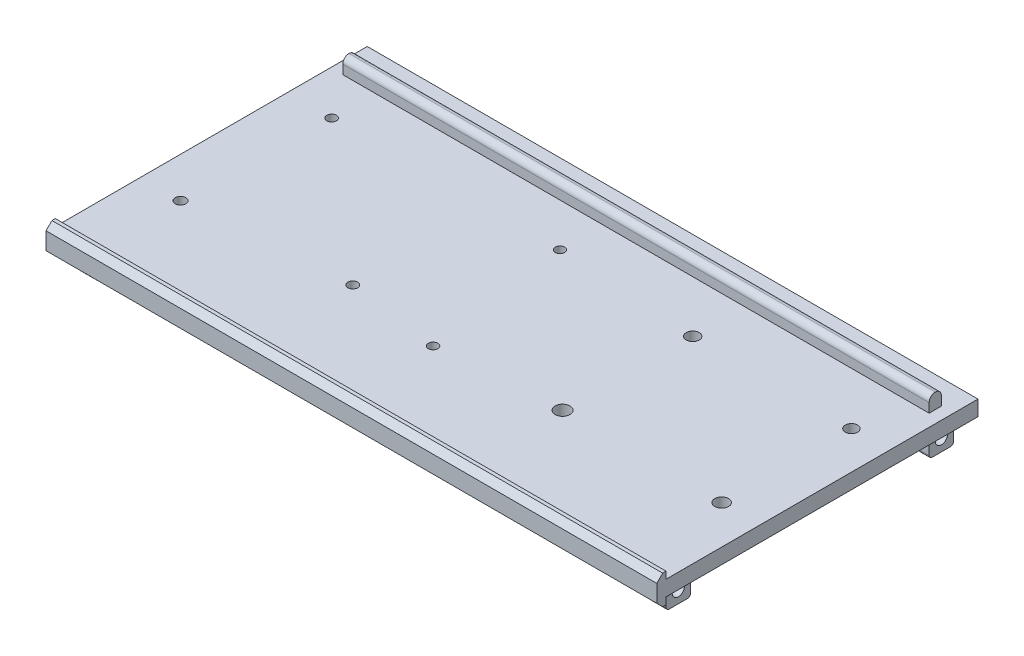
SolidWorks part; units mm, degrees
ref_plane "Alzado" through (0, 0, 0) normal (0, 0, 1) x (1, 0, 0)
ref_plane "Planta" through (0, 0, 0) normal (0, 1, 0) x (1, 0, 0)
ref_plane "Vista lateral" through (0, 0, 0) normal (1, 0, 0) x (0, 0, -1)
sketch "foto" plane through (0, 0, 0) normal (0, 1, 0) x (1, 0, 0)
  line L1 (15, 25) -> (75, 25) construction
  line L2 (15, 25) -> (15, -25) construction
  line L3 (15, -25) -> (75, -25) construction
  line L4 (75, 25) -> (75, -25) construction
  line L5 (-116.6, 26.67) -> (-15, 26.67) construction
  line L6 (-116.6, 26.67) -> (-116.6, -26.67) construction
  line L7 (-116.6, -26.67) -> (-15, -26.67) construction
  line L8 (-15, 26.67) -> (-15, -26.67) construction
  dimension "D1" = 60
  dimension "D2" = 50
  dimension "D3" = 25
  dimension "D4" = 15
  dimension "D5" = 53.34
  dimension "D6" = 101.6
  dimension "D7" = 15
  dimension "D8" = 26.67
sketch "Croquis3" plane through (0, 0, 0) normal (0, 1, 0) x (1, 0, 0)
  line L1 (-116.001, 50) -> (83.999, 50)
  line L2 (-116.001, 50) -> (-116.001, -50)
  line L3 (-116.001, -50) -> (83.999, -50)
  line L4 (83.999, 50) -> (83.999, -50)
  circle A0 centre (19.4896, 21.1007) radius 2.1242
  circle A1 centre (71.658, 20.902) radius 2.0314
  circle A2 centre (71.3776, -21.3107) radius 2.2649
  circle A3 centre (19.1425, -21.1883) radius 2.4502
  circle A4 centre (-101.5108, 23.8675) radius 1.5858
  circle A5 centre (-26.7755, 23.8801) radius 1.5354
  circle A6 centre (-20.2798, -24.1541) radius 1.5614
  circle A7 centre (-50.7247, -20.0103) radius 1.6096
  circle A8 centre (-102.8167, -24.3329) radius 1.7342
  dimension "D1" = 100
  dimension "D2" = 50
  dimension "D3" = 200
extrude "Saliente-Extruir1" add sketch "Croquis3" along normal blind 5
sketch "Croquis4" plane through (0, 5, 0) normal (0, 1, 0) x (1, 0, 0)
  circle A90 centre (-101.5108, 23.8675) radius 1.5858
  circle A91 centre (-26.7755, 23.8801) radius 1.5354
  circle A92 centre (-20.2798, -24.1541) radius 1.5614
  circle A93 centre (-50.7247, -20.0103) radius 1.6096
  circle A94 centre (-102.8167, -24.3329) radius 1.7342
  circle A95 centre (19.4896, 21.1007) radius 2.1242
  circle A96 centre (71.658, 20.902) radius 2.0314
  circle A97 centre (71.3776, -21.3107) radius 2.2649
  circle A98 centre (19.1425, -21.1883) radius 2.4502
  circle A99 centre (-101.5108, 23.8675) radius 3.5858
  circle A100 centre (-26.7755, 23.8801) radius 3.5354
  circle A101 centre (-50.7247, -20.0103) radius 3.6096
  circle A102 centre (-102.8167, -24.3329) radius 3.7342
  circle A103 centre (-20.2798, -24.1541) radius 3.5614
  circle A104 centre (19.1425, -21.1883) radius 4.4502
  circle A105 centre (19.4896, 21.1007) radius 4.1242
  circle A106 centre (71.658, 20.902) radius 4.0314
  circle A107 centre (71.3776, -21.3107) radius 4.2649
  dimension "D1" = 2
extrude "Saliente-Extruir2" add sketch "Croquis4" against normal blind 9
sketch "Croquis7" plane through (83.999, 0, 0) normal (1, 0, 0) x (0, 0, -1)
  line L0 (-50, 0) -> (50, 0) construction
  line L1 (-50, -7.5) -> (-70, -7.5) construction
  line L2 (-50, -7.5) -> (-50, 12.5) construction
  line L3 (-50, 12.5) -> (-70, 12.5) construction
  line L4 (-70, -7.5) -> (-70, 12.5) construction
  line L5 (-50, 5) -> (-50, 0) construction
  dimension "D1" = 7.5
  dimension "D2" = 20
  dimension "D3" = 20
sketch "Croquis8" plane through (83.999, 0, 0) normal (1, 0, 0) x (0, 0, -1)
  line L0 (-50, 5) -> (-52.133, 5)
  line L1 (-52.133, 5) -> (-52.133, 7.2643)
  line L2 (-52.133, 7.2643) -> (-53.25, 7.2643)
  line L3 (-53.25, 7.2643) -> (-55.1863, 5.328)
  line L4 (-55.1863, 5.328) -> (-55.1863, -0.328)
  line L5 (-55.1863, 2.5) -> (-37.6856, 2.5) construction
  line L6 (-53.25, -2.2643) -> (-55.1863, -0.328)
  line L7 (-52.133, -2.2643) -> (-53.25, -2.2643)
  line L8 (-52.133, 0) -> (-52.133, -2.2643)
  line L9 (-50, 0) -> (-52.133, 0)
  line L10 (-50, 5) -> (-50, 0)
extrude "Saliente-Extruir3" add sketch "Croquis8" against normal blind 200
sketch "Croquis9" plane through (0, 0, 0) normal (0, -1, 0) x (1, 0, 0)
  line L0 (-116.001, 52.133) -> (83.999, 52.133) construction
  line L1 (-112.001, 48.133) -> (-107.001, 48.133)
  line L2 (-112.001, 48.133) -> (-112.001, 40.133)
  line L3 (-112.001, 40.133) -> (-107.001, 40.133)
  line L4 (-107.001, 48.133) -> (-107.001, 40.133)
  line L5 (74.999, 40.133) -> (79.999, 40.133)
  line L6 (79.999, 48.133) -> (79.999, 40.133)
  line L7 (74.999, 48.133) -> (79.999, 48.133)
  line L8 (74.999, 48.133) -> (74.999, 40.133)
  line L9 (74.999, -46) -> (79.999, -46)
  line L10 (79.999, -38) -> (79.999, -46)
  line L11 (74.999, -38) -> (79.999, -38)
  line L12 (74.999, -38) -> (74.999, -46)
  line L13 (-112.001, -46) -> (-107.001, -46)
  line L14 (-107.001, -38) -> (-107.001, -46)
  line L15 (-112.001, -38) -> (-107.001, -38)
  line L16 (-112.001, -38) -> (-112.001, -46)
  line L17 (-116.001, -50) -> (-116.001, 52.133) construction
  line L18 (83.999, 52.133) -> (83.999, -50) construction
  line L19 (83.999, -50) -> (-116.001, -50) construction
  dimension "D1" = 8
  dimension "D2" = 5
  dimension "D3" = 4
  dimension "D6" = 4
  dimension "D7" = 4
  dimension "D8" = 4
  dimension "D4" = 2
  dimension "D5" = 2
extrude "Saliente-Extruir4" add sketch "Croquis9" along normal blind 8
fillet "Redondeo1" radius 1 8 edges at (-109.501, -8, 40.133) (-109.501, -8, 48.133) (-109.501, -8, -38) (-109.501, -8, -46) (77.499, -8, -38) (77.499, -8, -46) (77.499, -8, 40.133) (77.499, -8, 48.133)
fillet "Redondeo2" radius 2 9 edges at (71.3776, -4, 25.5756) (19.1425, -4, 25.6385) (-20.2798, -4, 27.7155) (-50.7247, -4, 23.6199) (-102.8167, -4, 28.0671) (71.658, -4, -16.8706) (19.4896, -4, -16.9765) (-26.7755, -4, -20.3447) (-101.5108, -4, -20.2817)
sketch "Croquis11" plane through (0, 0, 0) normal (0, -1, 0) x (1, 0, 0)
  line L0 (83.999, -50) -> (-116.001, -50) construction
  line L1 (-57.4359, -46) -> (-49.4359, -46)
  line L2 (-57.4359, -46) -> (-57.4359, -40)
  line L3 (-57.4359, -40) -> (-49.4359, -40)
  line L4 (-49.4359, -46) -> (-49.4359, -40)
  line L5 (42.5641, -40) -> (50.5641, -40)
  line L6 (42.5641, -46) -> (50.5641, -46)
  line L7 (42.5641, -46) -> (42.5641, -40)
  line L8 (50.5641, -46) -> (50.5641, -40)
  dimension "D1" = 4
  dimension "D2" = 6
  dimension "D3" = 8
  dimension "D4" = 2
extrude "Saliente-Extruir5" add sketch "Croquis11" along normal blind 8
fillet "Redondeo3" radius 2 4 edges at (-57.4359, -8, -43) (-49.4359, -8, -43) (42.5641, -8, -43) (50.5641, -8, -43)
sketch "Croquis12" plane through (0, 5, 0) normal (0, 1, 0) x (1, 0, 0)
  line L0 (-112.001, 38) -> (-112.001, 46) construction
  line L1 (-112.001, 42) -> (79.999, 42)
  line L2 (-112.001, 42) -> (-112.001, 38)
  line L3 (-112.001, 38) -> (79.999, 38)
  line L4 (79.999, 42) -> (79.999, 38)
extrude "Saliente-Extruir6" add sketch "Croquis12" along normal blind 5
fillet "Redondeo4" radius 2 2 edges at (-16.001, 10, -38) (-16.001, 10, -42)
sketch "Croquis13" plane through (-112.001, 0, 0) normal (-1, 0, 0) x (0, 0, 1)
  line L0 (-42, 0) -> (-42, -8) construction
  line L1 (-38, 0) -> (-46, 0) construction
  line L2 (-39, -8) -> (-45, -8) construction
  line L3 (44.133, 0) -> (44.133, -8) construction
  line L4 (48.133, 0) -> (40.133, 0) construction
  line L5 (47.133, -8) -> (41.133, -8) construction
  circle A0 centre (-42, -4) radius 2
  circle A1 centre (44.133, -4) radius 2
extrude "Cortar-Extruir3" cut sketch "Croquis13" against normal blind 6
sketch "Croquis14" plane through (79.999, 0, 0) normal (1, 0, 0) x (0, 0, -1)
  line L0 (-44.133, 0) -> (-44.133, -8) construction
  line L1 (-48.133, 0) -> (-40.133, 0) construction
  line L2 (-41.133, -8) -> (-47.133, -8) construction
  line L3 (42, 0) -> (42, -8) construction
  line L4 (38, 0) -> (46, 0) construction
  line L5 (45, -8) -> (39, -8) construction
  circle A0 centre (-44.133, -4) radius 2
  circle A1 centre (42, -4) radius 2
extrude "Cortar-Extruir4" cut sketch "Croquis14" against normal blind 6
sketch "Croquis15" plane through (0, 0, -46) normal (0, 0, -1) x (-1, 0, 0)
  line L0 (-46.5641, 0) -> (-46.5641, -8) construction
  line L1 (-42.5641, 0) -> (-50.5641, 0) construction
  line L2 (-44.5641, -8) -> (-48.5641, -8) construction
  line L3 (53.4359, 0) -> (53.4359, -8) construction
  line L4 (57.4359, 0) -> (49.4359, 0) construction
  line L5 (55.4359, -8) -> (51.4359, -8) construction
  circle A0 centre (-46.5641, -4) radius 2
  circle A1 centre (53.4359, -4) radius 2
extrude "Cortar-Extruir5" cut sketch "Croquis15" against normal blind 6
